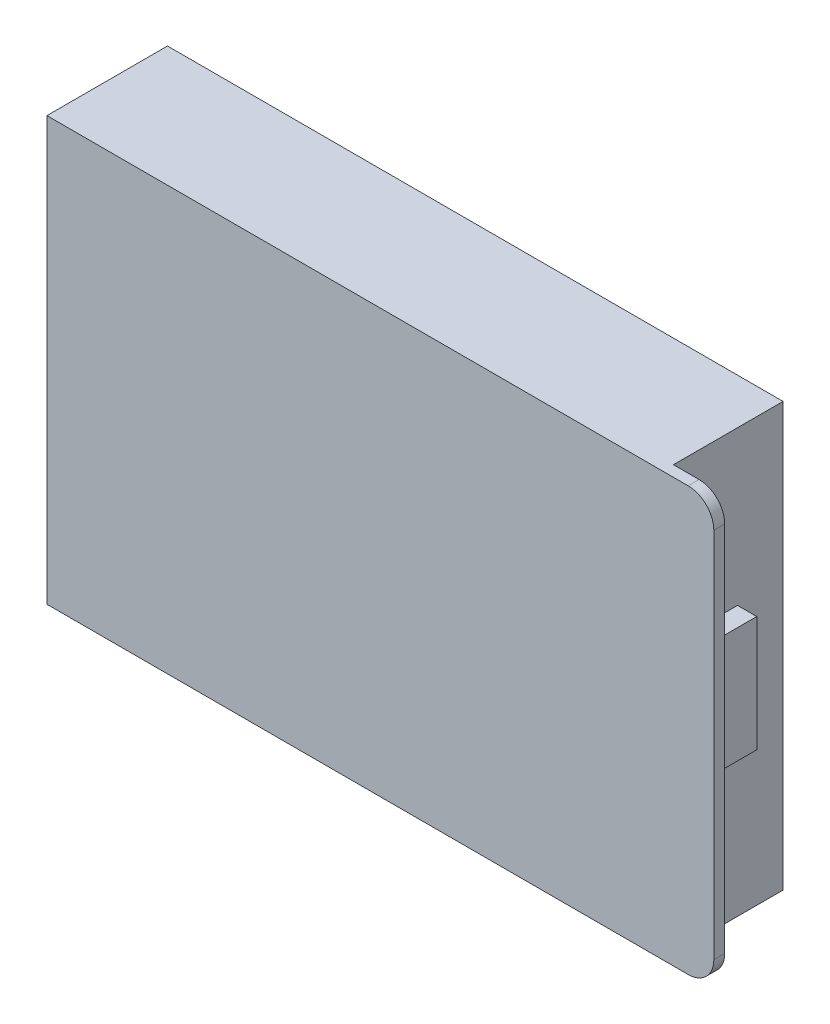
SolidWorks part; units mm, degrees
ref_plane "Front Plane" through (0, 0, 0) normal (0, 0, 1) x (1, 0, 0)
ref_plane "Top Plane" through (0, 0, 0) normal (0, 1, 0) x (1, 0, 0)
ref_plane "Right Plane" through (0, 0, 0) normal (1, 0, 0) x (0, 0, -1)
sketch "Sketch1" plane through (0, 0, 0) normal (0, 0, 1) x (1, 0, 0)
  line L1 (-48, -33) -> (48, -33)
  line L2 (-48, -33) -> (-48, 33)
  line L3 (-48, 33) -> (48, 33)
  line L4 (48, -33) -> (48, 33)
  line L5 (-48, -33) -> (48, 33) construction
  line L6 (-48, 33) -> (48, -33) construction
  point P0 (0, 0)
  dimension "D1" = 96
  dimension "D2" = 66
extrude "Boss-Extrude1" add sketch "Sketch1" along normal blind 17.1
sketch "Sketch2" plane through (0, 0, 17.1) normal (0, 0, 1) x (1, 0, 0)
  line L0 (-48, -33) -> (48, -33) construction
  line L1 (-48, 33) -> (52, 33)
  line L2 (-48, 33) -> (-48, -33)
  line L3 (-48, -33) -> (52, -33)
  line L4 (56, 29) -> (56, -29)
  arc A0 (52, -33) -> (56, -29) centre (52, -29) ccw
  arc A1 (52, 33) -> (56, 29) centre (52, 29) cw
  point P11 (56, 33)
  dimension "D2" = 4
  dimension "D3" = 4
  dimension "D1" = 104
extrude "Boss-Extrude2" add sketch "Sketch2" along normal blind 1.7
sketch "Sketch3" plane through (48, 0, 0) normal (1, 0, 0) x (0, 0, -1)
  line L0 (-17.1, -33) -> (-17.1, 33) construction
  line L1 (-17.1, 9) -> (-7.1, 9)
  line L2 (-17.1, 9) -> (-17.1, -9)
  line L3 (-17.1, -9) -> (-7.1, -9)
  line L4 (-7.1, 9) -> (-7.1, -9)
  line L5 (-7.1, 0) -> (-17.1, 0) construction
  line L6 (-17.1, -33) -> (0, -33) construction
  line L7 (-17.1, 33) -> (0, 33) construction
  dimension "D1" = 18
  dimension "D2" = 10
extrude "Boss-Extrude3" add sketch "Sketch3" along normal blind 3
